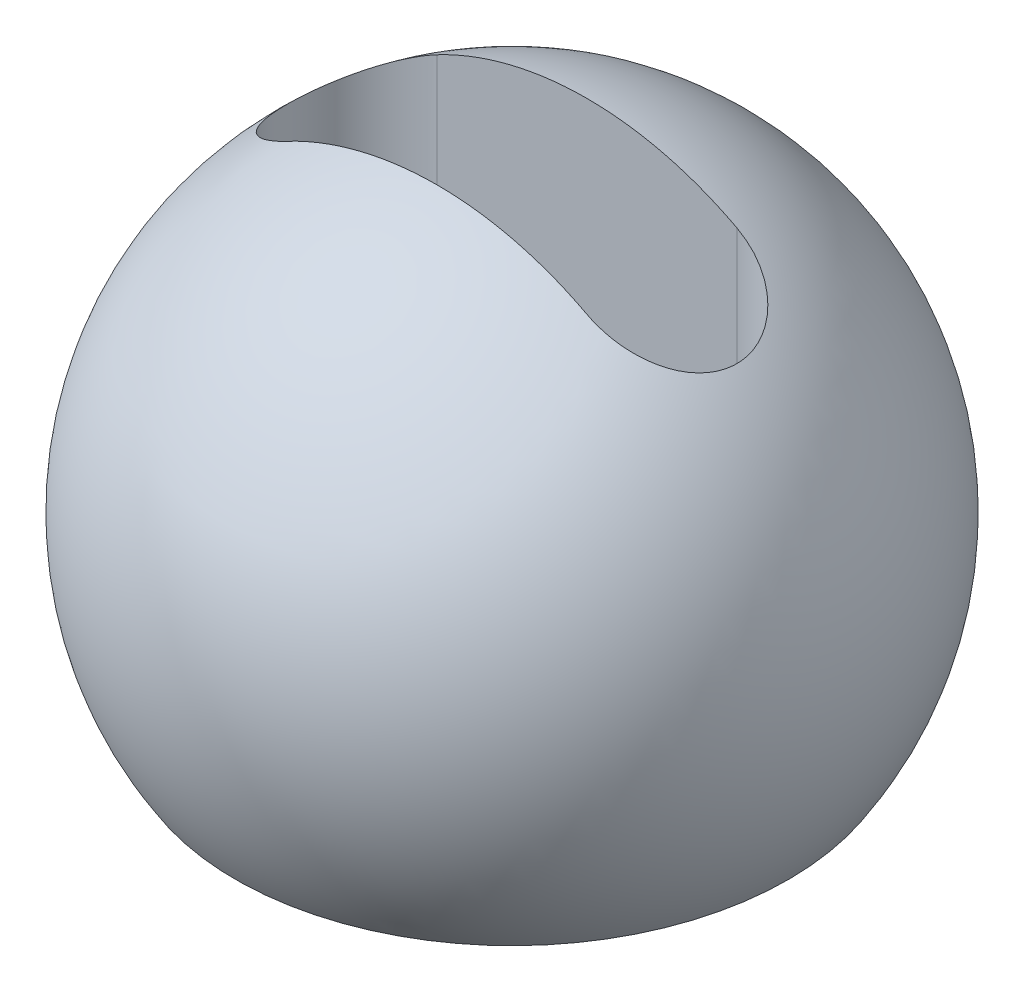
SolidWorks part; units mm, degrees
ref_plane "Front Plane" through (0, 0, 0) normal (0, 0, 1) x (1, 0, 0)
ref_plane "Top Plane" through (0, 0, 0) normal (0, 1, 0) x (1, 0, 0)
ref_plane "Right Plane" through (0, 0, 0) normal (1, 0, 0) x (0, 0, -1)
sketch "Sketch1" plane through (0, 0, 0) normal (0, 0, 1) x (1, 0, 0)
  line L0 (0, 4.7305) -> (0, 20.099) construction
  line L1 (46.0977, -30) -> (0, -30)
  line L2 (0, 55) -> (0, -30)
  arc A0 (0, 55) -> (46.0977, -30) centre (0, 0) cw
  point P2 (0, 0)
  point P6 (27.9538, -30)
  point P7 (0, 5.6876)
  point P8 (0, 0)
  dimension "D1" = 55
  dimension "D2" = 30
revolve "Revolve1" add sketch "Sketch1" angle 360 about L0
sketch "Sketch3" plane through (0, 0, 0) normal (0, 1, 0) x (1, 0, 0)
  line L0 (-25, 0) -> (25, 0) construction
  line L1 (-25, 12.5) -> (25, 12.5)
  line L2 (-25, -12.5) -> (25, -12.5)
  arc A0 (-25, 12.5) -> (-25, -12.5) centre (-25, 0) ccw
  arc A1 (25, -12.5) -> (25, 12.5) centre (25, 0) ccw
  circle A2 centre (-25, 0) radius 12.5
  circle A3 centre (25, 0) radius 12.5
  point P2 (0, 0)
  dimension "D1" = 25
  dimension "D2" = 50
extrude "Cut-Extrude4" cut sketch "Sketch3" along normal blind 80 from offset 15 contours L1 A1 L2 A0
sketch "Sketch6" plane through (0, 0, 0) normal (0, 1, 0) x (1, 0, 0)
  circle A0 centre (-25, 0) radius 12.5
  circle A1 centre (25, 0) radius 12.5
  dimension "D2" = 25
  dimension "D3" = 25
  dimension "D1" = 50
  dimension "D4" = 25
  dimension "D5" = 25
extrude "Cut-Extrude6" cut sketch "Sketch6" against normal blind 80 from offset 15
